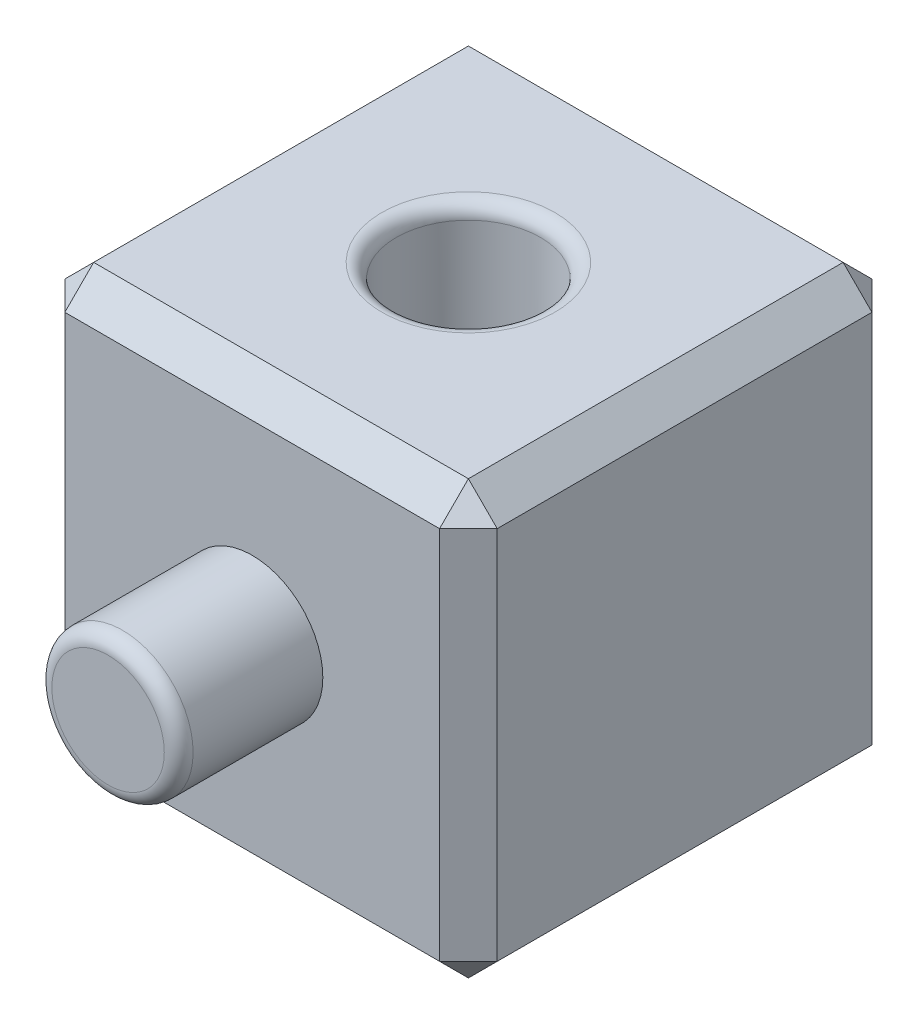
SolidWorks part; units mm, degrees
ref_plane "Front Plane" through (0, 0, 0) normal (0, 0, 1) x (1, 0, 0)
ref_plane "Top Plane" through (0, 0, 0) normal (0, 1, 0) x (1, 0, 0)
ref_plane "Right Plane" through (0, 0, 0) normal (1, 0, 0) x (0, 0, -1)
sketch "Sketch1" plane through (0, 0, 0) normal (0, 0, 1) x (1, 0, 0)
  line L1 (0, 0) -> (15, 0)
  line L2 (0, 0) -> (0, 15)
  line L3 (0, 15) -> (15, 15)
  line L4 (15, 0) -> (15, 15)
  dimension "D1" = 15
  dimension "D2" = 15
extrude "Boss-Extrude1" add sketch "Sketch1" along normal blind 15
sketch "Sketch2" plane through (0, 0, 15) normal (0, 0, 1) x (1, 0, 0)
  line L0 (0, 0) -> (15, 15)
  circle A0 centre (7.5, 7.5) radius 2.45
  dimension "D1" = 4.9
extrude "Boss-Extrude2" add sketch "Sketch2" along normal blind 5 contours L0 A0 | L0 A0 region at (6.7647, 8.2353, 15) region at (8.2353, 6.7647, 15)
sketch "Sketch7" plane through (0, 0, 0) normal (-1, 0, 0) x (0, 0, 1)
  line L0 (0, 0) -> (15, 15) construction
  circle A0 centre (7.5, 7.5) radius 2.5
  dimension "D1" = 5
extrude "Cut-Extrude1" cut sketch "Sketch7" against normal blind 4
sketch "Sketch13" plane through (0, 15, 0) normal (0, 1, 0) x (1, 0, 0)
  line L0 (0, -15) -> (15, 0) construction
  circle A0 centre (7.5, -7.5) radius 2.5
  dimension "D1" = 5
extrude "Cut-Extrude6" cut sketch "Sketch13" against normal blind 4 contours A0
sketch "Sketch16" plane through (0, 0, 0) normal (0, 0, -1) x (-1, 0, 0)
  line L0 (-15, 0) -> (0, 15) construction
  circle A0 centre (-7.5, 7.5) radius 2.5
  dimension "D1" = 5
extrude "Cut-Extrude7" cut sketch "Sketch16" against normal blind 4
chamfer "Chamfer1" distance 1 angle 45 12 edges at (7.5, 15, 15) (15, 15, 7.5) (15, 7.5, 15) (15, 0, 7.5) (7.5, 0, 15) (15, 7.5, 0) (7.5, 0, 0) (0, 7.5, 15) (0, 0, 7.5) (0, 15, 7.5) (7.5, 15, 0) (0, 7.5, 0)
fillet "Fillet1" radius 0.5 4 edges at (0, 7.5, 10) (9.95, 7.5, 20) (7.5, 15, 10) (5, 7.5, 0)
